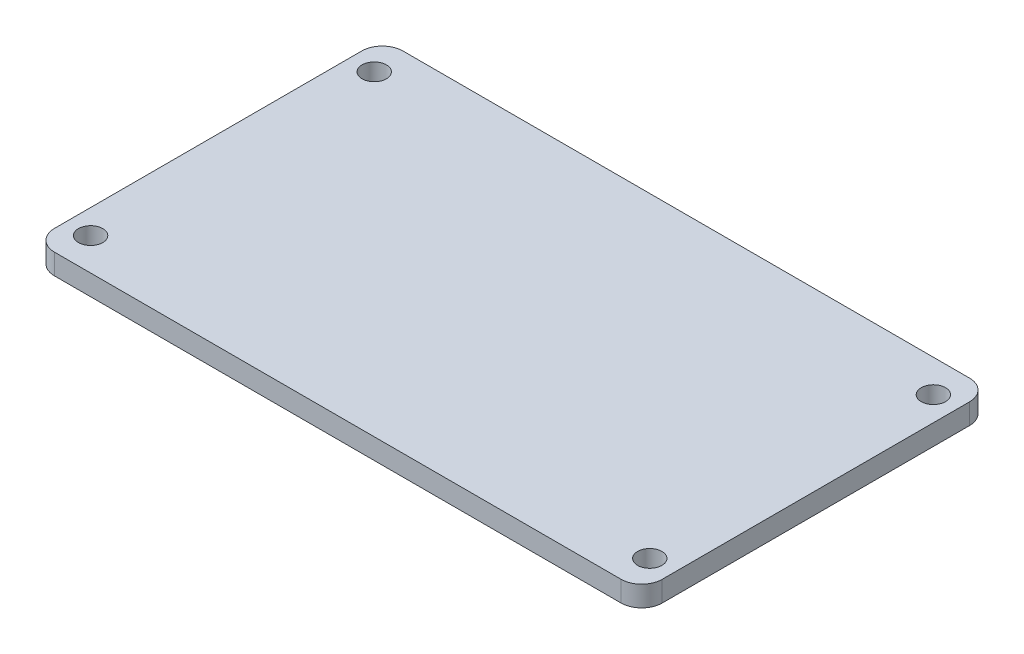
SolidWorks part; units mm, degrees
material "Silicon"
ref_plane "Front Plane" through (0, 0, 0) normal (0, 0, 1) x (1, 0, 0)
ref_plane "Top Plane" through (0, 0, 0) normal (0, 1, 0) x (1, 0, 0)
ref_plane "Right Plane" through (0, 0, 0) normal (1, 0, 0) x (0, 0, -1)
sketch "Sketch1" plane through (0, 0, 0) normal (0, 1, 0) x (1, 0, 0)
  line L0 (-34.5, 17.5) -> (34.5, -17.5) construction
  line L1 (-34.96, -21.5) -> (34.96, -21.5)
  line L2 (-37.5, -18.96) -> (-37.5, 18.96)
  line L3 (-34.96, 21.5) -> (34.96, 21.5)
  line L4 (37.5, -18.96) -> (37.5, 18.96)
  line L5 (-37.5, -21.5) -> (37.5, 21.5) construction
  line L6 (-37.5, 21.5) -> (37.5, -21.5) construction
  line L7 (-34.5, -17.5) -> (34.5, 17.5) construction
  circle A0 centre (-34.5, 17.5) radius 1.5
  circle A1 centre (-34.5, -17.5) radius 1.5
  circle A2 centre (34.5, -17.5) radius 1.5
  circle A3 centre (34.5, 17.5) radius 1.5
  arc A4 (34.96, 21.5) -> (37.5, 18.96) centre (34.96, 18.96) cw
  arc A5 (37.5, -18.96) -> (34.96, -21.5) centre (34.96, -18.96) cw
  arc A6 (-34.96, -21.5) -> (-37.5, -18.96) centre (-34.96, -18.96) cw
  arc A7 (-37.5, 18.96) -> (-34.96, 21.5) centre (-34.96, 18.96) cw
  point P0 (0, 0)
  dimension "D5" = 3
  dimension "D6" = 2.54
  dimension "D1" = 43
  dimension "D2" = 75
  dimension "D3" = 69
  dimension "D4" = 35
extrude "Boss-Extrude1" add sketch "Sketch1" along normal blind 2.54
